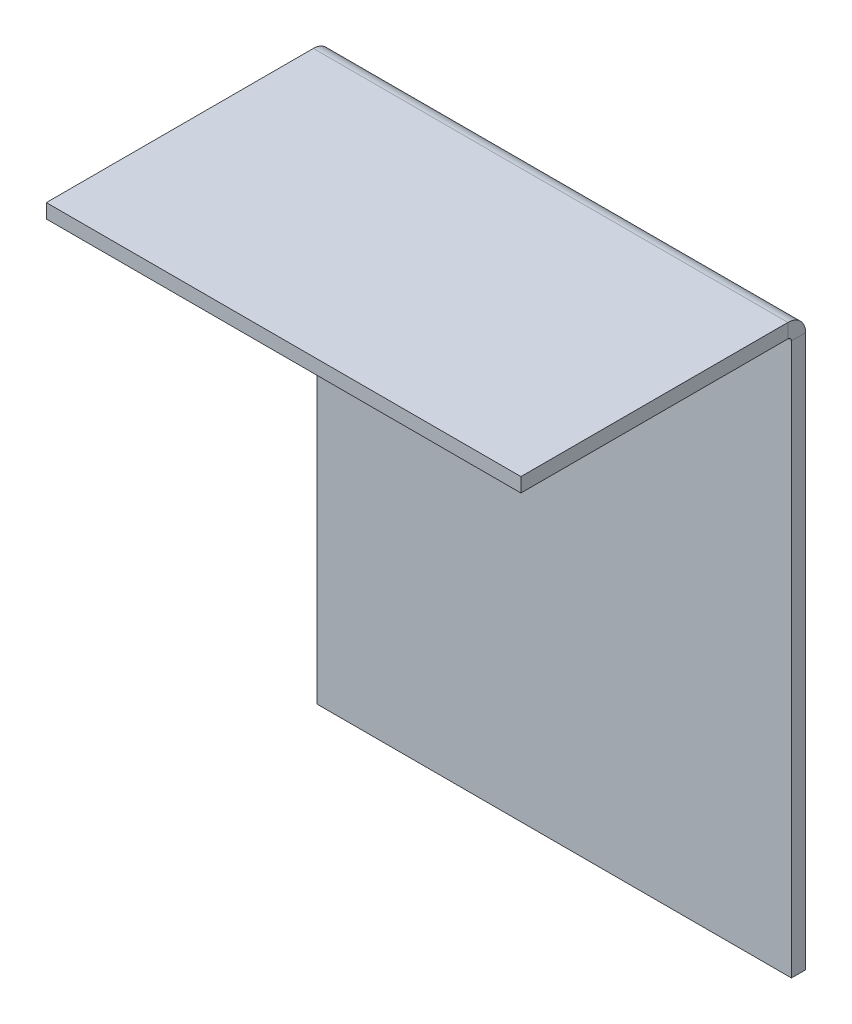
SolidWorks part; units mm, degrees
note: The reader was unsure of these and kept them because the rebuilt part matched: flange length of "边线-法兰1".
material "08优质冷轧钢板"
ref_plane "前视基准面" through (0, 0, 0) normal (0, 0, 1) x (1, 0, 0)
ref_plane "上视基准面" through (0, 0, 0) normal (0, 1, 0) x (1, 0, 0)
ref_plane "右视基准面" through (0, 0, 0) normal (1, 0, 0) x (0, 0, -1)
other "Configuration Table"
sketch "草图1" plane through (0, 0, 0) normal (0, 0, 1) x (1, 0, 0)
  line L1 (-50, 60) -> (50, 60)
  line L2 (-50, 60) -> (-50, -60)
  line L3 (-50, -60) -> (50, -60)
  line L4 (50, 60) -> (50, -60)
  line L5 (-50, 60) -> (50, -60) construction
  line L6 (-50, -60) -> (50, 60) construction
  point P0 (0, 0)
  dimension "D1" = 100
  dimension "D2" = 120
base flange "基体-法兰1" sketch "草图1" thickness 3 reverse thickness direction no parameters "D1"=0.7366
edge flange "边线-法兰1" sketch "草图8" flange angle 90 flange length 60 flange position material inside bend radius 0.7366 thickness 3 relief rectangular parameters "D6"=10
sketch "草图8" plane through (0, 60, 0) normal (0, 1, 0) x (-1, 0, 0)
  line L0 (-50, 0) -> (50, 0) construction
  line L1 (-50, 0) -> (50, 0)
  line L2 (-50, 0) -> (-50, 57)
  line L3 (-50, 57) -> (50, 57)
  line L4 (50, 57) -> (50, 0)
bend "边线折弯1" bend radius 0.7366 bend angle 90 parameters "D5"=1
sketch "折弯-线1" [suppressed] plane through (0, 0, 0) normal (0, 1, 0) x (1, 0, 0)
sketch "边界框1" [suppressed] plane through (0, 0, 0) normal (0, 1, 0) x (1, 0, 0)
sheet metal parameters "钣金6" thickness 3 parameters "D1"=0.7366
flat pattern "平板型式6" [suppressed]
sketch "折弯-线2" plane through (0, 0, 0) normal (0, 1, 0) x (1, 0, 0)
sketch "边界框2" [suppressed] plane through (0, 0, 0) normal (0, 1, 0) x (1, 0, 0)
sheet metal parameters "钣金7" thickness 3 parameters "D1"=0.7366
flat pattern "平板型式6"
sketch "折弯-线2" plane through (0, 0, 0) normal (0, 0, 1) x (1, 0, 0)
  line L0 (50, 58.02) -> (-50, 58.02) construction
  line L1 (50, 58.02) -> (-50, 58.02) construction
sketch3d "边界框2" [suppressed]
  line L0 (50, 116.04, 0) -> (50, -60, 0) construction
  line L1 (-50, 116.04, 0) -> (-50, -60, 0) construction
  line L2 (50, 116.04, 0) -> (-50, 116.04, 0) construction
  line L3 (50, -60, 0) -> (-50, -60, 0) construction
bend of the flat pattern "展平-<边线折弯1>1"
